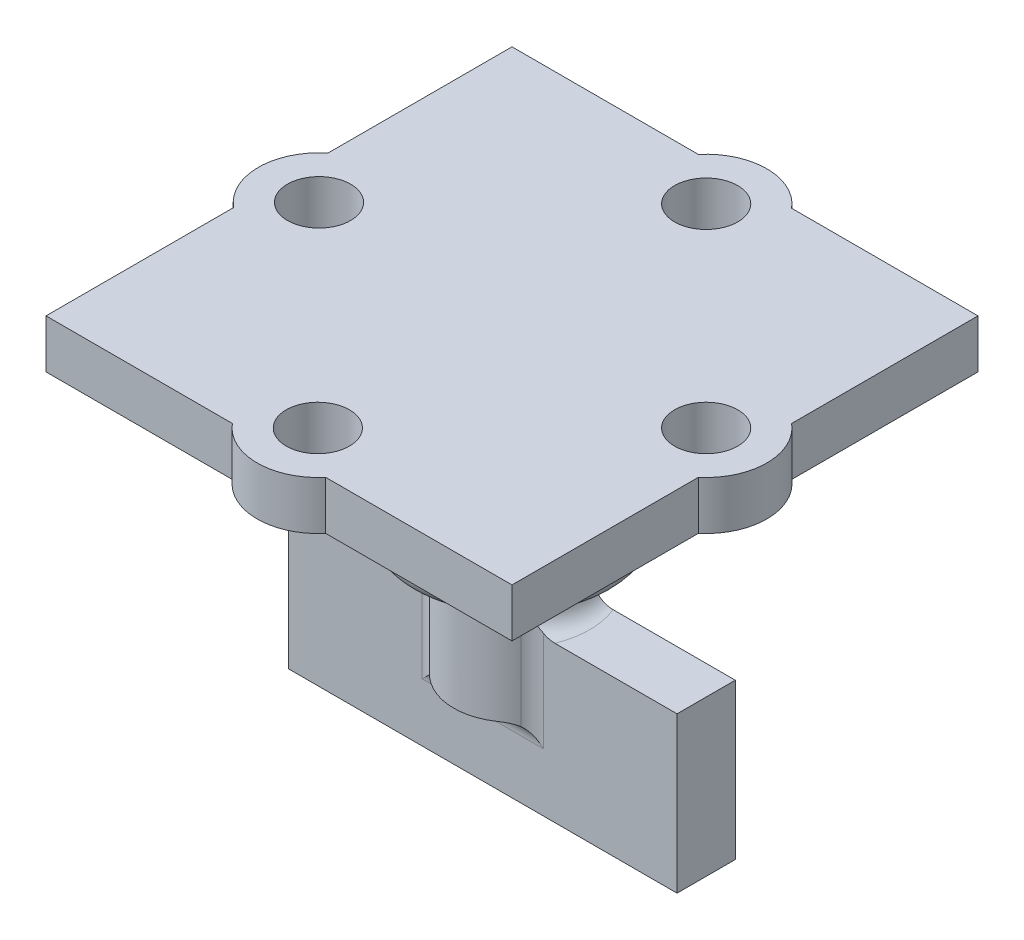
SolidWorks part; units mm, degrees
ref_plane "Спереди" through (0, 0, 0) normal (0, 0, 1) x (1, 0, 0)
ref_plane "Сверху" through (0, 0, 0) normal (0, 1, 0) x (1, 0, 0)
ref_plane "Справа" through (0, 0, 0) normal (1, 0, 0) x (0, 0, -1)
sketch "Sketch1" plane through (0, 0, 0) normal (0, 1, 0) x (1, 0, 0)
  line L0 (-24, -4.6689) -> (-24, -24)
  line L1 (-24, 24) -> (-4.8023, 24)
  line L2 (-24, 24) -> (-24, 5.0436)
  line L3 (-24, -24) -> (-4.8023, -24)
  line L4 (24, 24) -> (24, 4.8023)
  line L5 (-24, 24) -> (24, -24) construction
  line L6 (-24, -24) -> (24, 24) construction
  line L7 (-16, 16) -> (-4.8023, 16)
  line L8 (-16, 16) -> (-16, 4.9342)
  line L9 (-16, -16) -> (-4.8023, -16)
  line L10 (16, 16) -> (16, 4.8023)
  line L11 (-16, 16) -> (16, -16) construction
  line L12 (-16, -16) -> (16, 16) construction
  line L13 (-16, -4.5595) -> (-16, -16)
  line L14 (4.8023, 16) -> (16, 16)
  line L15 (4.8023, 24) -> (24, 24)
  line L16 (16, -4.8023) -> (16, -16)
  line L17 (4.8023, -16) -> (16, -16)
  line L18 (4.8023, -24) -> (24, -24)
  line L19 (24, -4.8023) -> (24, -24)
  circle A0 centre (-20.0657, 0.1873) radius 3.25
  circle A1 centre (0, 20) radius 3.25
  circle A2 centre (20, 0) radius 3.25
  circle A3 centre (0, -20) radius 3.25
  arc A4 (12, -16) -> (6.1732, -19.0234) centre (0, 0) ccw construction
  arc A5 (-24, 5.0436) -> (-24, -4.6689) centre (-20.0657, 0.1873) ccw
  arc A6 (-4.8023, 16) -> (4.8023, 16) centre (0, 20) ccw
  arc A7 (16, 4.8023) -> (16, -4.8023) centre (20, 0) ccw
  arc A8 (4.8023, -16) -> (-4.8023, -16) centre (0, -20) ccw
  arc A9 (-16, -4.5595) -> (-16, 4.9342) centre (-20.0657, 0.1873) ccw
  arc A10 (4.8023, 24) -> (-4.8023, 24) centre (0, 20) ccw
  arc A11 (24, -4.8023) -> (24, 4.8023) centre (20, 0) ccw
  arc A12 (-4.8023, -24) -> (4.8023, -24) centre (0, -20) ccw
  point P0 (0, 0)
  point P6 (0, 0)
  dimension "D3" = 40
  dimension "D4" = 6.5
  dimension "D5" = 12.5
  dimension "D6" = 6.5
  dimension "D7" = 12.5
  dimension "D8" = 6.5
  dimension "D9" = 12.5
  dimension "D10" = 6.5
  dimension "D11" = 12.5
  dimension "D1" = 48
  dimension "D2" = 32
  dimension "D12" = 32
extrude "Boss-Extrude1" add sketch "Sketch1" along normal blind 5 contours L4 A11 L19 L18 A12 L3 L0 A5 L2 L1 A10 L15 | A8 L9 L13 A9 L8 L7 A6 L14 L10 A7 L16 L17 | A1 | A3 | A2 | A0
ref_plane "Plane1" through (0, -65, 0) normal (0, -1, 0) x (-1, 0, 0)
sketch "Sketch2" plane through (0, 0, 0) normal (0, -1, 0) x (1, 0, 0)
  line L1 (-16.3247, -16.4535) -> (16.3247, -16.4535)
  line L2 (-16.3247, -16.4535) -> (-16.3247, 16.4535)
  line L3 (-16.3247, 16.4535) -> (16.3247, 16.4535)
  line L4 (16.3247, -16.4535) -> (16.3247, 16.4535)
  line L5 (-16.3247, -16.4535) -> (16.3247, 16.4535) construction
  line L6 (-16.3247, 16.4535) -> (16.3247, -16.4535) construction
  point P0 (0, 0)
extrude "Boss-Extrude2" add sketch "Sketch2" against normal up to surface (5 mm away) up to face at (20, 5, 3.25)
sketch "Sketch3" plane through (0, 0, 0) normal (0, -1, 0) x (-1, 0, 0)
  circle A0 centre (0, 0) radius 10.5672
extrude "Boss-Extrude3" add sketch "Sketch3" along normal blind 15
sketch "Sketch4" plane through (0, -15, 0) normal (0, -1, 0) x (-1, 0, 0)
  circle A0 centre (0, 0) radius 6
extrude "Boss-Extrude4" add sketch "Sketch4" along normal blind 12
sketch "Sketch5" plane through (0, 0, 0) normal (1, 0, 0) x (0, 0, -1)
  line L2 (-6, -27) -> (6, -27) construction
  line L3 (-3, -19) -> (3, -19)
  line L4 (-3, -19) -> (-3, -35)
  line L5 (-3, -35) -> (3, -35)
  line L6 (3, -19) -> (3, -35)
  line L7 (-3, -19) -> (3, -35) construction
  line L8 (-3, -35) -> (3, -19) construction
  point P0 (0, -27)
extrude "Boss-Extrude5" add sketch "Sketch5" along normal mid plane 40
fillet "Fillet4" radius 2 6 edges at (-5.1962, -23, 3) (5.1962, -23, 3) (0, -27, 3) (-5.1962, -23, -3) (5.1962, -23, -3) (0, -27, -3)
fillet "Fillet1" radius 2 3 edges at (0, -15, -6) (0, 0, 10.5672) (0, -15, -10.5672)
fillet "Fillet5" radius 2 2 edges at (-6, -19, 0) (6, -19, 0)
